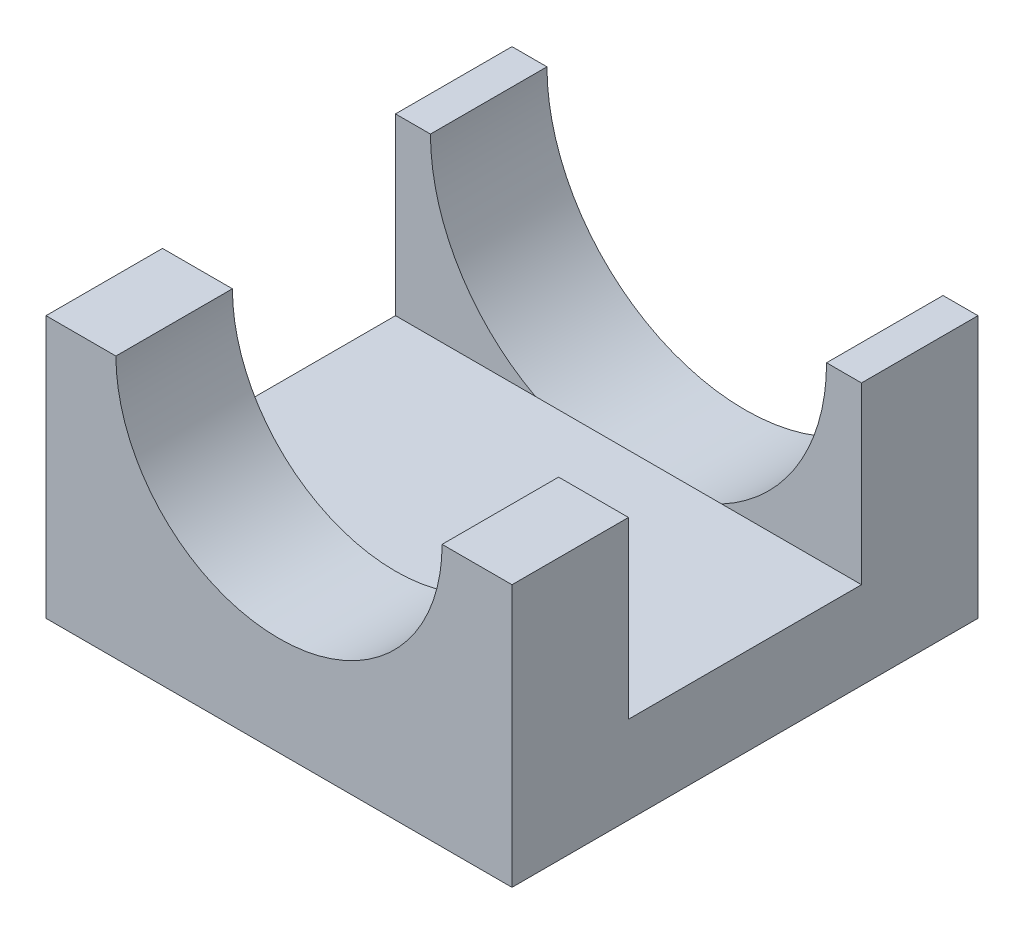
SolidWorks part; units mm, degrees
ref_plane "Front Plane" through (0, 0, 0) normal (0, 0, 1) x (1, 0, 0)
ref_plane "Top Plane" through (0, 0, 0) normal (0, 1, 0) x (1, 0, 0)
ref_plane "Right Plane" through (0, 0, 0) normal (1, 0, 0) x (0, 0, -1)
sketch "Sketch1" plane through (0, 0, 0) normal (0, 0, 1) x (1, 0, 0)
  line L1 (-20, 22.5) -> (20, 22.5)
  line L2 (-20, 22.5) -> (-20, -22.5)
  line L3 (-20, -22.5) -> (20, -22.5)
  line L4 (20, 22.5) -> (20, -22.5)
  line L5 (-20, 22.5) -> (20, -22.5) construction
  line L6 (-20, -22.5) -> (20, 22.5) construction
  point P0 (0, 0)
  dimension "D1" = 40
  dimension "D2" = 45
extrude "Boss-Extrude1" add sketch "Sketch1" along normal blind 40
sketch "Sketch2" plane through (0, 0, 0) normal (0, 0, -1) x (-1, 0, 0)
  circle A0 centre (0, 0) radius 17
  dimension "D1" = 34
extrude "Cut-Extrude1" cut sketch "Sketch2" against normal blind 10
ref_axis "Axis1" through (0, 0, 57.2332) along (0, 0, -1)
sketch "Sketch3" plane through (0, 0, 40) normal (0, 0, 1) x (1, 0, 0)
  circle A0 centre (0, 0) radius 14
  dimension "D1" = 28
extrude "Cut-Extrude2" cut sketch "Sketch3" against normal blind 10
sketch "Sketch4" plane through (0, 0, 40) normal (0, 0, 1) x (1, 0, 0)
  line L0 (-20, 0) -> (20, 0)
  line L1 (-20, 22.5) -> (-20, -22.5) construction
  line L2 (20, -22.5) -> (20, 22.5) construction
  line L3 (20, 22.5) -> (-20, 22.5) construction
  line L4 (20, 0) -> (20, 22.5)
  line L5 (-20, 22.5) -> (-20, 0)
  line L6 (20, 22.5) -> (-20, 22.5)
extrude "Cut-Extrude3" cut sketch "Sketch4" against normal through all
sketch "Sketch5" plane through (0, 0, 0) normal (0, 1, 0) x (1, 0, 0)
  line L0 (-20, 0) -> (-20, -40) construction
  line L1 (-20, -10) -> (20, -10)
  line L2 (-20, -10) -> (-20, -30)
  line L3 (-20, -30) -> (20, -30)
  line L4 (20, -10) -> (20, -30)
  line L5 (20, 0) -> (20, -40) construction
  line L6 (-20, 0) -> (-17, 0) construction
  line L7 (-20, -40) -> (-14, -40) construction
  point P12 (-17, -40)
  dimension "D1" = 10
  dimension "D2" = 10
extrude "Cut-Extrude4" cut sketch "Sketch5" against normal blind 15
